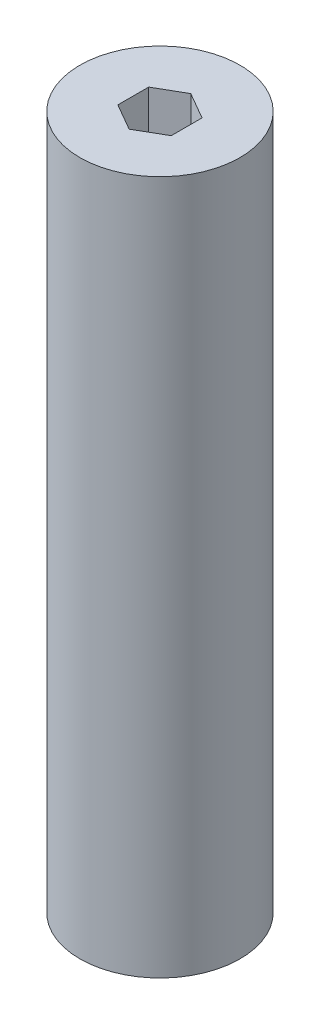
SolidWorks part; units mm, degrees
ref_plane "Front Plane" through (0, 0, 0) normal (0, 0, 1) x (1, 0, 0)
ref_plane "Top Plane" through (0, 0, 0) normal (0, 1, 0) x (1, 0, 0)
ref_plane "Right Plane" through (0, 0, 0) normal (1, 0, 0) x (0, 0, -1)
sketch "Sketch1" plane through (0, 0, 0) normal (0, 1, 0) x (1, 0, 0)
  circle A0 centre (0, 0) radius 19.05
  dimension "D1" = 38.1
extrude "Boss-Extrude1" add sketch "Sketch1" along normal blind 165.1
sketch "Sketch2" plane through (0, 165.1, 0) normal (0, 1, 0) x (1, 0, 0)
  line L1 (0, 7.3323) -> (-6.35, 3.6662)
  line L2 (-6.35, 3.6662) -> (-6.35, -3.6662)
  line L3 (-6.35, -3.6662) -> (0, -7.3323)
  line L4 (0, -7.3323) -> (6.35, -3.6662)
  line L5 (6.35, -3.6662) -> (6.35, 3.6662)
  line L6 (6.35, 3.6662) -> (0, 7.3323)
  circle A0 centre (0, 0) radius 6.35 construction
  dimension "D1" = 12.7
extrude "Cut-Extrude1" cut sketch "Sketch2" against normal up to surface (165.1 mm away) up to face at (0, 0, 19.05)
